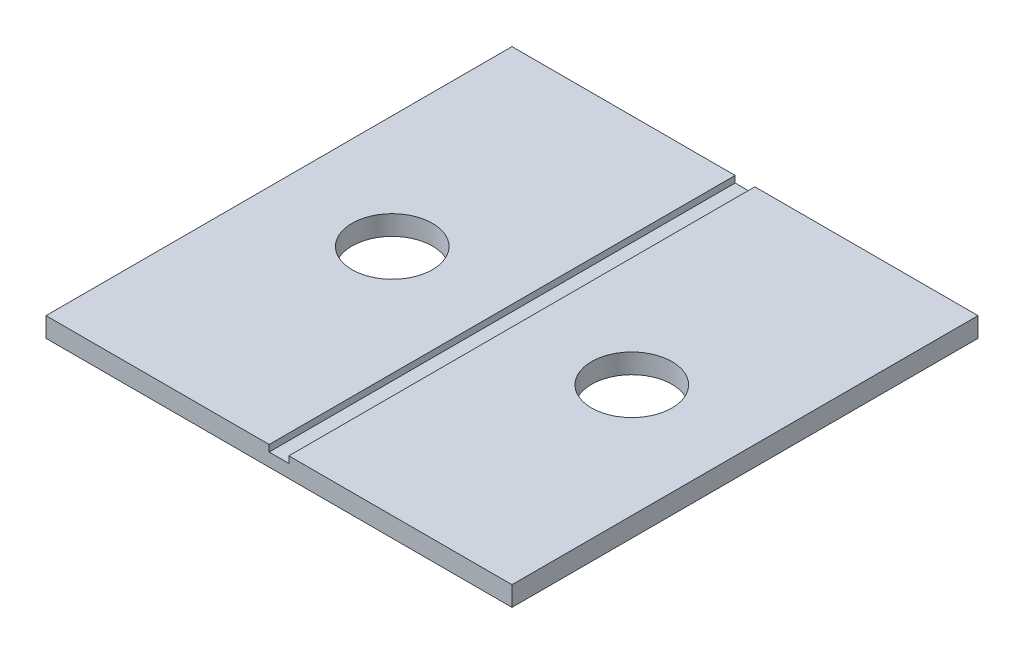
SolidWorks part; units mm, degrees
material "Pine"
ref_plane "Front Plane" through (0, 0, 0) normal (0, 0, 1) x (1, 0, 0)
ref_plane "Top Plane" through (0, 0, 0) normal (0, 1, 0) x (1, 0, 0)
ref_plane "Right Plane" through (0, 0, 0) normal (1, 0, 0) x (0, 0, -1)
sketch "Panel" plane through (0, 0, 0) normal (0, 1, 0) x (1, 0, 0)
  line L0 (69, 284) -> (69, 0) construction
  line L1 (0, 0) -> (284, 0)
  line L2 (0, 0) -> (0, 284)
  line L3 (0, 284) -> (284, 284)
  line L4 (284, 0) -> (284, 284)
  line L5 (0, 142) -> (284, 142) construction
  line L6 (215, 284) -> (215, 0) construction
  circle A0 centre (69, 142) radius 24.5
  circle A1 centre (215, 142) radius 24.5
  dimension "D5" = 49
  dimension "D6" = 49
  dimension "D3" = 69
  dimension "D4" = 69
  dimension "width" = 284
  dimension "height" = 284
extrude "Panel Ply" add sketch "Panel" along normal blind 12
sketch "Sketch2" plane through (0, 12, 0) normal (0, 1, 0) x (1, 0, 0)
  line L0 (284, 284) -> (0, 284) construction
  line L1 (136, 284) -> (148, 284)
  line L2 (136, 284) -> (136, 0)
  line L3 (136, 0) -> (148, 0)
  line L4 (148, 284) -> (148, 0)
  line L5 (0, 0) -> (284, 0) construction
  line L6 (0, 284) -> (0, 0) construction
  dimension "D1" = 12
  dimension "D2" = 136
extrude "Center Brance Housing Cut" cut sketch "Sketch2" against normal blind 4
equation "\"D3@Panel\" = 276 / 4"
equation "\"D4@Panel\" = 276 / 4"
equation "\"LENGTH\" = 1000mm"
equation "\"WIDTH\" = 300mm"
equation "\"HEIGHT\" = 300mm"
equation "\"HOUSING_DEPTH\" = 4mm"
equation "\"PLY\"= 12mm"
equation "\"CENTER_BRACE_LENGTH\" = 393mm"
equation "\"PANEL_WIDTH\"= \"LENGTH\" - \"CENTER_BRACE_LENGTH\" * 2 - \"PLY\" * 4"
equation "\"PANEL_SMALL_HEIGHT\" = 70mm"
equation "\"PORT_WIDTH\" = 90mm"
equation "\"PORT_RADIUS\" = 15mm"
equation "\"PORT_BRACE_HEIGHT\" = 92mm"
equation "\"DOWEL_SIZE\" = 0.25in"
equation "\"DOWEL_OFFSET\" = 30mm"
equation "\"width@Panel\" = \"WIDTH\" - \"PLY\" * 2 + \"HOUSING_DEPTH\" * 2"
equation "\"height@Panel\" = \"HEIGHT\" - \"PLY\" * 2 + \"HOUSING_DEPTH\" * 2"
equation "\"D1@Sketch2\"=\"PLY\""
equation "\"D2@Sketch2\"=\"width@Panel\" / 2 - \"PLY\" / 2"
equation "\"D1@Center Brance Housing Cut\"=\"HOUSING_DEPTH\""
